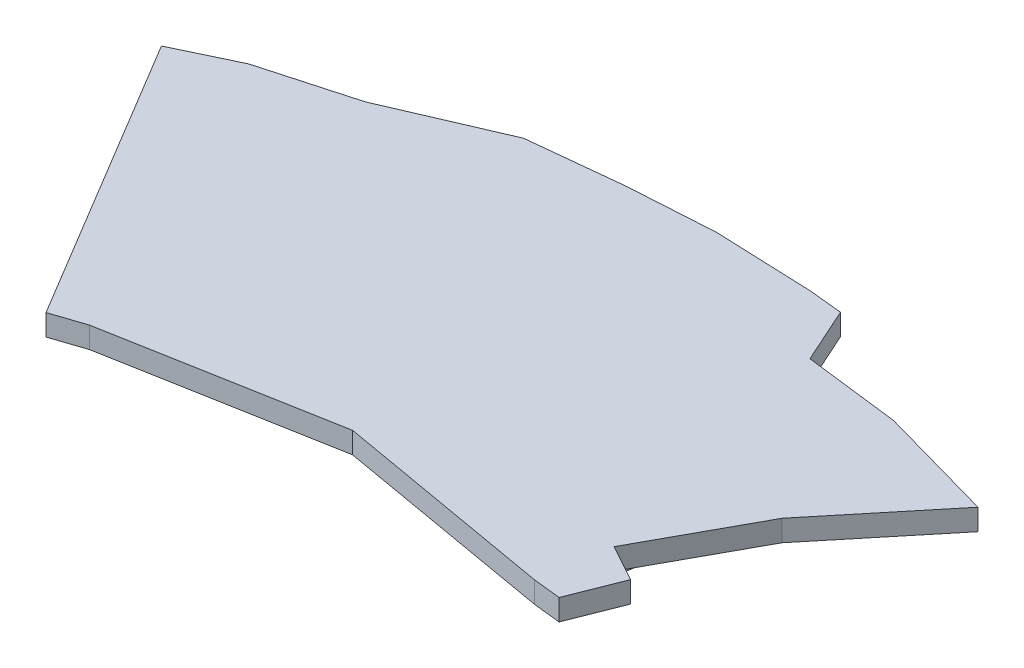
SolidWorks part; units mm, degrees
ref_plane "Спереди" through (0, 0, 0) normal (0, 0, 1) x (1, 0, 0)
ref_plane "Сверху" through (0, 0, 0) normal (0, 1, 0) x (1, 0, 0)
ref_plane "Справа" through (0, 0, 0) normal (1, 0, 0) x (0, 0, -1)
sketch "Sketch1" plane through (0, 0, 0) normal (0, 1, 0) x (1, 0, 0)
  line L0 (-16.549, 27.0761) -> (-10.9862, 29.7217)
  line L4 (-2.3972, 32.1207) -> (8.0131, 36.6023)
  line L6 (8.5342, 33.4389) -> (17.1591, 34.6302)
  line L8 (16.7327, 37.5159) -> (24.7622, 38.0129)
  line L9 (24.7622, 38.0129) -> (33.9231, 37.6554)
  line L10 (33.9231, 37.6554) -> (37.1114, 37.3372)
  line L11 (37.1114, 37.3372) -> (39.47, 32.1029)
  line L12 (39.47, 32.1029) -> (48.4337, 31.0077)
  line L13 (48.4337, 31.0077) -> (59.4784, 27.9132)
  line L14 (59.4784, 27.9132) -> (51.1602, 17.7931)
  line L15 (51.1602, 17.7931) -> (45.5707, 7.5752)
  line L17 (44.5054, 1.1246) -> (23.7834, 4.7438)
  line L18 (23.7834, 4.7438) -> (2.8079, 0.9393)
  line L19 (2.8079, 0.9393) -> (-0.2529, -0.0846)
  line L20 (-0.2529, -0.0846) -> (-16.549, 27.0761)
  line L21 (-10.8918, 26.5778) -> (-0.7342, 29.2797)
  line L22 (-0.7342, 29.2797) -> (5.6405, 5.662)
  line L23 (5.6405, 5.662) -> (-2.3972, 3.4894)
  line L24 (-10.8918, 26.5778) -> (-5.7935, 9.15)
  line L25 (7.7055, 33.4389) -> (18.0074, 34.7772)
  line L26 (18.0074, 34.7772) -> (21.3451, 10.8014)
  line L27 (21.3451, 10.8014) -> (11.0012, 9.2753)
  line L28 (11.0012, 9.2753) -> (7.7055, 33.4389)
  line L29 (23.9941, 35.2159) -> (23.1104, 10.9961)
  line L30 (23.1104, 10.9961) -> (33.2335, 10.4179)
  line L31 (33.2335, 10.4179) -> (34.2485, 34.6302)
  line L32 (34.2485, 34.6302) -> (23.9941, 35.2159)
  line L33 (38.3098, 29.3631) -> (48.452, 27.6537)
  line L34 (48.452, 27.6537) -> (44.1593, 3.7084)
  line L35 (44.1593, 3.7084) -> (34.1439, 5.1983)
  line L36 (34.1439, 5.1983) -> (38.3098, 29.3631)
  line L37 (-10.9862, 29.7217) -> (-2.3972, 32.1207)
  line L38 (8.0131, 36.6023) -> (16.7327, 37.5159)
  line L39 (45.5707, 7.5752) -> (49.0233, 5.6516)
  line L40 (49.0233, 5.6516) -> (47.1195, 0.8374)
  line L41 (47.1195, 0.8374) -> (44.5054, 1.1246)
extrude "Boss-Extrude1" add sketch "Sketch1" against normal blind 0.1 contours L21 L24 L20 L23 L22 region at (-2.4947, 0, -16.4789)
extrude "Boss-Extrude2" add sketch "Sketch1<4>" against normal blind 0.3 separate body contours L28 L27 L26 L25 region at (14.5102, 0, -22.0594)
sketch "Sketch1<4>" plane through (0, 0, 0) normal (0, 1, 0) x (1, 0, 0) same geometry as "Sketch1"
extrude "Boss-Extrude3" add sketch "Sketch1<6>" against normal blind 1.6 separate body contours L31 L32 L29 L30 region at (28.6476, 0, -22.841)
sketch "Sketch1<6>" plane through (0, 0, 0) normal (0, 1, 0) x (1, 0, 0) same geometry as "Sketch1"
extrude "Boss-Extrude4" add sketch "Sketch1<7>" against normal blind 1 separate body contours L36 L35 L34 L33 region at (41.2651, 0, -16.514)
sketch "Sketch1<7>" plane through (0, 0, 0) normal (0, 1, 0) x (1, 0, 0) same geometry as "Sketch1"
extrude "Boss-Extrude6" add sketch "Sketch1<9>" along normal blind 2 contours L38 L4 L37 L0 L20 L24 L21 L22 L23 L19 L18 L17 L15 L14 L13 L12 L11 L10 L9 L8 L32 L31 L30 L29 L27 L28 L25 L26 L35 L36 L33 L34 | L21 L24 L20 L23 L22 | L28 L27 L26 L25 | L31 L32 L29 L30 | L36 L35 L34 L33 region at (21.1031, 0, -19.9027) region at (-2.4947, 0, -16.4789) region at (14.5102, 0, -22.0594) region at (28.6476, 0, -22.841) region at (41.2651, 0, -16.514)
sketch "Sketch1<9>" plane through (0, 0, 0) normal (0, 1, 0) x (1, 0, 0) same geometry as "Sketch1"
